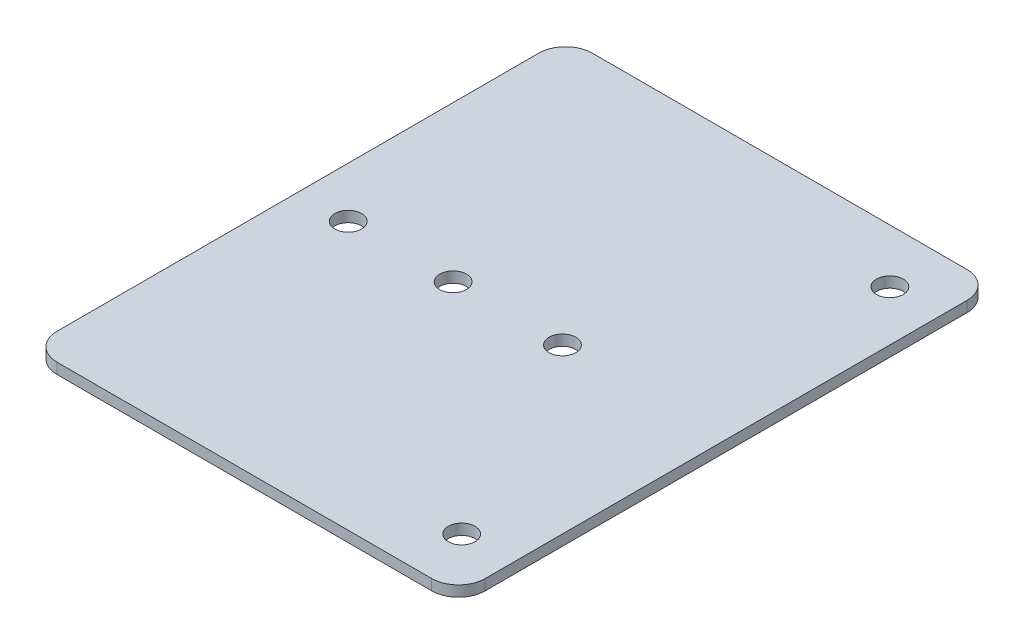
SolidWorks part; units mm, degrees
material "ABS"
ref_plane "Front Plane" through (0, 0, 0) normal (0, 0, 1) x (1, 0, 0)
ref_plane "Top Plane" through (0, 0, 0) normal (0, 1, 0) x (1, 0, 0)
ref_plane "Right Plane" through (0, 0, 0) normal (1, 0, 0) x (0, 0, -1)
sketch "Sketch1" plane through (0, 0, 0) normal (0, 1, 0) x (1, 0, 0)
  line L9 (30.6, 0) -> (-30.6, 0) construction
  line L10 (-35, 50) -> (35, 50)
  line L11 (-40, 45) -> (-40, -45)
  line L12 (-35, -50) -> (35, -50)
  line L13 (40, 45) -> (40, -45)
  line L14 (-40, 50) -> (40, -50) construction
  line L15 (-40, -50) -> (40, 50) construction
  line L17 (30.6, 40) -> (30.6, -40) construction
  line L20 (-18, 19.52) -> (12, 19.52) construction
  line L21 (-18, 27.92) -> (16.42, 27.92) construction
  line L22 (-18, 27.92) -> (-18, 19.52) construction
  line L23 (-18, -5.5) -> (16.42, -5.5) construction
  line L24 (16.42, 27.92) -> (16.42, -5.5) construction
  line L25 (-0.79, -5.5) -> (-0.79, 14.52) construction
  line L26 (12, 19.52) -> (12, 14.52) construction
  line L27 (12, 14.52) -> (-18, 14.52) construction
  line L28 (-18, 14.52) -> (-18, -5.5) construction
  line L29 (0, 27.92) -> (0, 0) construction
  arc A0 (35, 50) -> (40, 45) centre (35, 45) cw
  arc A1 (35, -50) -> (40, -45) centre (35, -45) ccw
  arc A2 (-40, -45) -> (-35, -50) centre (-35, -45) ccw
  arc A3 (-35, 50) -> (-40, 45) centre (-35, 45) ccw
  circle A4 centre (-30.6, 0) radius 2.5
  circle A5 centre (30.6, 40) radius 2.5
  circle A6 centre (30.6, -40) radius 2.5
  circle A7 centre (9.42, 0) radius 2.5
  circle A8 centre (-11, 0) radius 2.5
  point P0 (0, 0)
  point P31 (-18, -5.5)
  dimension "D7" = 34.42
  dimension "D3" = 5
  dimension "D5" = 5
  dimension "D14" = 5
  dimension "D1" = 80
  dimension "D2" = 100
  dimension "D4" = 80
  dimension "D6" = 61.2
  dimension "D8" = 33.42
  dimension "D9" = 30
  dimension "D10" = 8.4
  dimension "D11" = 5
  dimension "D12" = 5.5
  dimension "D13" = 7
  dimension "D15" = 18
extrude "Boss-Extrude1" add sketch "Sketch1" along normal blind 2
sketch "Sketch6" plane through (0, 2, 0) normal (0, 1, 0) x (1, 0, 0)
  line L0 (-36.4704, -29.7789) -> (28.5296, -49.7789)
  line L1 (-40, 45) -> (-40, -45) construction
  line L2 (-35, -50) -> (35, -50) construction
  line L3 (-40, 0) -> (40, 0) construction
  line L4 (40, -45) -> (40, 45) construction
  line L5 (-40, -25) -> (-40, -50)
  line L6 (-40, -50) -> (30, -50)
  line L7 (-40, 50) -> (30, 50)
  line L8 (-40, 25) -> (-40, 50)
  line L9 (-36.4704, 29.7789) -> (28.5296, 49.7789)
  arc A1 (-40, -25) -> (-36.4704, -29.7789) centre (-35, -25) ccw
  arc A2 (28.5296, -49.7789) -> (30, -50) centre (30, -45) ccw
  arc A3 (28.5296, 49.7789) -> (30, 50) centre (30, 45) cw
  arc A4 (-40, 25) -> (-36.4704, 29.7789) centre (-35, 25) cw
  dimension "D1" = 10
  dimension "D2" = 10
  dimension "D3" = 25
  dimension "D4" = 10
